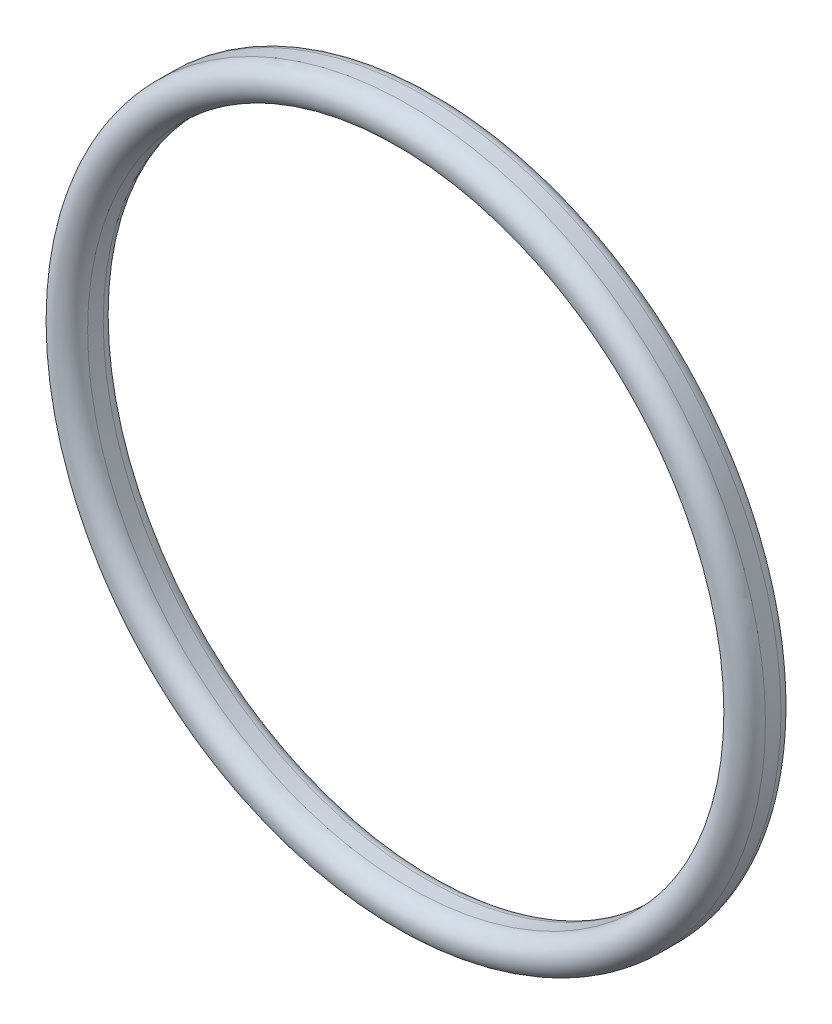
SolidWorks part; units mm, degrees
material "Rubber"
ref_plane "Front" through (0, 0, 0) normal (0, 0, 1) x (1, 0, 0)
ref_plane "Top" through (0, 0, 0) normal (0, 1, 0) x (1, 0, 0)
ref_plane "Right" through (0, 0, 0) normal (1, 0, 0) x (0, 0, -1)
ref_axis "Axis1" through (-84.4107, 0, 0) along (1, 0, 0)
ref_axis "Axis2" through (0, 64.3378, 0) along (0, -1, 0)
ref_axis "Axis3" through (0, 0, -102.329) along (0, 0, 1)
sketch "Sketch1" plane through (0, 0, 0) normal (1, 0, 0) x (0, 0, -1)
  line L0 (0, 0) -> (-4.0654, 0) construction
  line L1 (-4.3, 27.1) -> (0, 27.1) construction
  line L2 (-4.3, 27.1) -> (-4.3, 30) construction
  line L3 (-4.3, 30) -> (0, 30) construction
  line L4 (0, 27.1) -> (0, 30) construction
  line L6 (-2.314, 27.1) -> (-1, 27.1)
  line L8 (-2.314, 30) -> (-1, 30)
  line L9 (0, 28.1) -> (0, 29)
  arc A0 (-2.314, 30) -> (-2.314, 27.1) centre (-2.314, 28.55) ccw
  arc A1 (-1, 27.1) -> (0, 28.1) centre (-1, 28.1) ccw
  arc A2 (-1, 30) -> (0, 29) centre (-1, 29) cw
  dimension "D1" = 1
  dimension "D2" = 3.764
  dimension "D4" = 4.3
  dimension "D5" = 2.9
  dimension "D3" = 30
revolve "Revolve1" add sketch "Sketch1" angle 360 about L0
sketch "Sketch2" plane through (0, 0, 0) normal (1, 0, 0) x (0, 0, -1)
  line L0 (0, 0) -> (-7.4565, 0) construction
  circle A0 centre (-1.765, 27.965) radius 1.765
  dimension "D1" = 3.53
  dimension "D2" = 26.2
  dimension "D3" = 1.765
revolve "Revolve2" [suppressed] add sketch "Sketch2" angle 360 about L0
equation "\"D3@Sketch2\" = \"D1@Sketch2\"/2"
